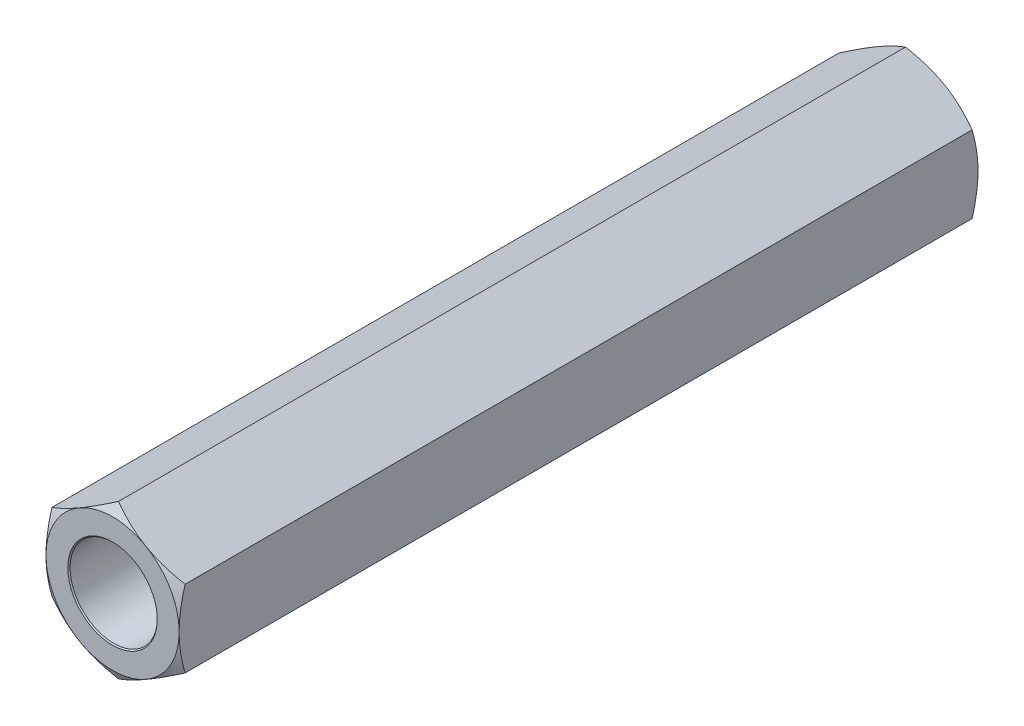
SolidWorks part; units mm, degrees
ref_plane "Front Plane" through (0, 0, 0) normal (0, 0, 1) x (1, 0, 0)
ref_plane "Top Plane" through (0, 0, 0) normal (0, 1, 0) x (1, 0, 0)
ref_plane "Right Plane" through (0, 0, 0) normal (1, 0, 0) x (0, 0, -1)
sketch "Sketch3" plane through (0, 0, 0) normal (1, 0, 0) x (0, 0, -1)
  line L0 (-19.05, 0) -> (19.05, 0) construction
  line L1 (0, 3.175) -> (0, -3.175) construction
  line L2 (-19.05, 2.0828) -> (-19.05, -2.0828) construction
  point P2 (9.525, 0)
  point P3 (-9.525, 0)
  dimension "Length" = 38.1
  dimension "Min Thread Length" = 9.525
  dimension "D1" = 9.525
  dimension "Thread Dia" = 4.1656
  dimension "Hex" = 6.35
sketch "Sketch1" plane through (0, 0, 0) normal (0, 0, 1) x (1, 0, 0)
  line L1 (0, 3.6662) -> (-3.175, 1.8331)
  line L2 (-3.175, 1.8331) -> (-3.175, -1.8331)
  line L3 (-3.175, -1.8331) -> (0, -3.6662)
  line L4 (0, -3.6662) -> (3.175, -1.8331)
  line L5 (3.175, -1.8331) -> (3.175, 1.8331)
  line L6 (3.175, 1.8331) -> (0, 3.6662)
  circle A0 centre (0, 0) radius 3.175 construction
  circle A1 centre (0, 0) radius 2.0828
extrude "Extrude1" add sketch "Sketch1" along normal up to vertex (19.05 mm away) and the other way up to vertex (19.05 mm away) up to point (0, 0, 19.05) other way up to point (0, 0, -19.05)
sketch "Sketch11" plane through (0, 0, -19.05) normal (0, 0, -1) x (-1, 0, 0)
  circle A0 centre (0, 0) radius 2.0828 construction
  circle A1 centre (0, 0) radius 2.0828
curve "Helix/Spiral1" pitch 0.7937 height 38.8938 turns 49 parameters "Pitch"=0.7937
sketch "Sketch12" plane through (0, 0, 0) normal (1, 0, 0) x (0, 0, -1)
  line L0 (19.7445, 2.0828) -> (19.05, 2.0828)
  line L1 (19.7445, 2.0828) -> (19.4469, 1.5672)
  line L2 (19.4469, 1.5672) -> (19.3477, 1.5672)
  line L3 (19.3477, 1.5672) -> (19.05, 2.0828)
  line L4 (19.3973, 1.5672) -> (19.3973, 2.0828) construction
  line L5 (19.5957, 1.825) -> (19.1988, 1.825) construction
  dimension "D1" = 0.0992
  dimension "D2" = 0.3969
  dimension "D3" = 60
sweep "Sweep1" [suppressed] add profiles "Sketch12" path "Helix/Spiral1"
sketch "Sketch6" plane through (0, 0, -19.05) normal (0, 0, -1) x (-1, 0, 0)
  line L6 (0, 3.6662) -> (-3.175, 1.8331)
  line L7 (-3.175, 1.8331) -> (-3.175, -1.8331)
  line L8 (-3.175, -1.8331) -> (0, -3.6662)
  line L9 (0, -3.6662) -> (3.175, -1.8331)
  line L10 (3.175, -1.8331) -> (3.175, 1.8331)
  line L11 (3.175, 1.8331) -> (0, 3.6662)
  line L12 (0, 3.6662) -> (-3.175, 1.8331)
  line L13 (-3.175, 1.8331) -> (-3.175, -1.8331)
  line L14 (-3.175, -1.8331) -> (0, -3.6662)
  line L15 (0, -3.6662) -> (3.175, -1.8331)
  line L16 (3.175, -1.8331) -> (3.175, 1.8331)
  line L17 (3.175, 1.8331) -> (0, 3.6662)
  dimension "D1" = 0
extrude "Extrude2" [suppressed] cut sketch "Sketch6" along normal through all
sketch "Sketch7" plane through (0, 0, -19.05) normal (0, 0, -1) x (-1, 0, 0)
  circle A2 centre (0, 0) radius 2.1336
  circle A3 centre (0, 0) radius 2.1336
  dimension "D1" = 0.0508
extrude "Extrude3" cut sketch "Sketch7" against normal through all draft 43
sketch "Sketch8" plane through (0, 0, -19.05) normal (0, 0, -1) x (-1, 0, 0)
  circle A0 centre (0, 0) radius 3.175 construction
  circle A1 centre (0, 0) radius 3.175
extrude "Extrude4" cut sketch "Sketch8" against normal through all draft 60 flip side to cut
mirror "Mirror1" about plane through (0, 0, 0) normal (0, 0, 1) of "Extrude2", "Extrude3", "Extrude4"
sketch "Sketch9" [suppressed] plane through (0, 0, 0) normal (1, 0, 0) x (0, 0, -1)
  line L1 (-9.525, 2.1336) -> (9.525, 2.1336)
  line L2 (-9.525, 2.1336) -> (-9.525, 0)
  line L3 (-9.525, 0) -> (9.525, 0)
  line L4 (9.525, 2.1336) -> (9.525, 0)
  line L7 (-19.05, 0) -> (19.05, 0) construction
revolve "Revolve" [suppressed] add sketch "Sketch9" angle 360 about L0
sketch "Sketch10" [suppressed] plane through (0, 0, 0) normal (1, 0, 0) x (0, 0, -1)
  line L0 (19.05, 2.0828) -> (9.525, 2.0828)
  line L1 (-19.05, 2.0828) -> (-9.525, 2.0828)
  line L2 (9.525, 2.0828) -> (9.525, -2.0828)
  line L3 (-19.05, -2.1336) -> (-9.525, -2.1336)
  line L4 (-9.525, 2.0828) -> (-9.525, -2.1336)
  line L5 (9.525, -2.0828) -> (19.05, -2.0828)
equation "\"D1@Sketch3\" = \"Min Thread Length@Sketch3\""
equation "\"D3@Helix/Spiral1\" = \"Length@Sketch3\"+\"Pitch@Helix/Spiral1\""
equation "\"D1@Sketch12\" = \"Pitch@Helix/Spiral1\"*.125"
equation "\"D2@Sketch12\" = \"Pitch@Helix/Spiral1\"*.5"
